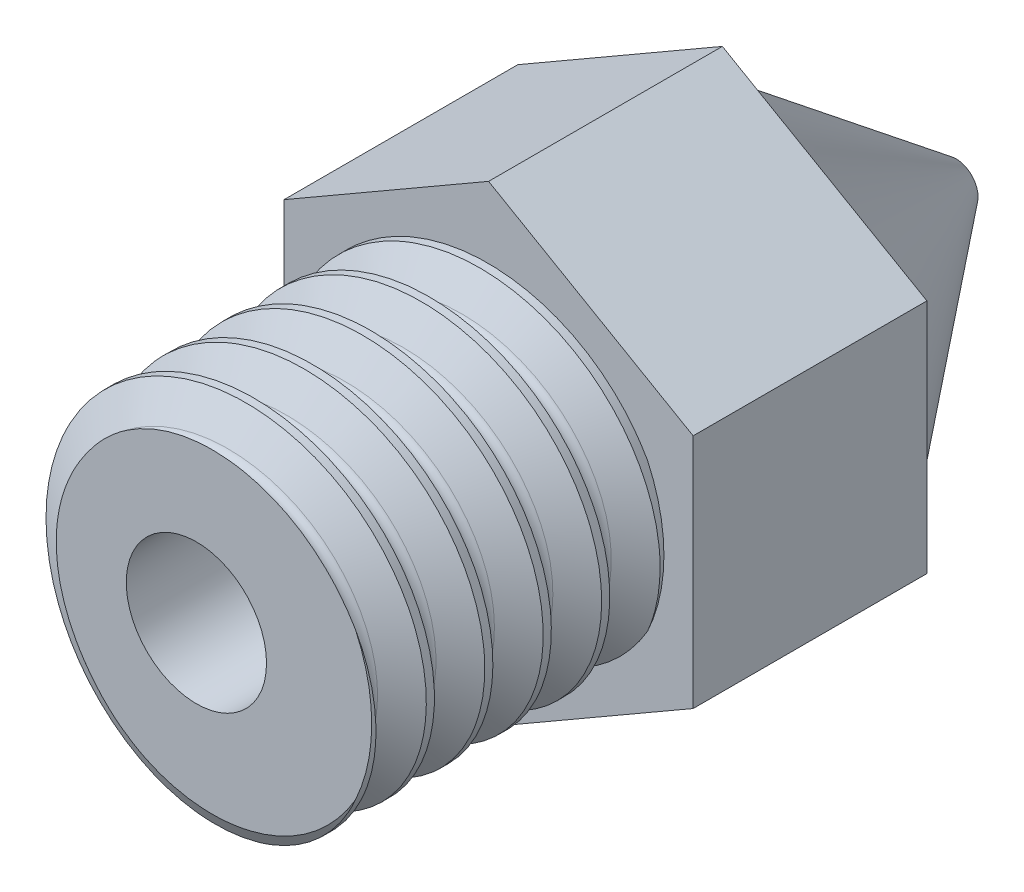
SolidWorks part; units mm, degrees
material "Brass"
ref_plane "Front Plane" through (0, 0, 0) normal (0, 0, 1) x (1, 0, 0)
ref_plane "Top Plane" through (0, 0, 0) normal (0, 1, 0) x (1, 0, 0)
ref_plane "Right Plane" through (0, 0, 0) normal (1, 0, 0) x (0, 0, -1)
sketch "Sketch1" plane through (0, 0, 0) normal (0, 0, 1) x (1, 0, 0)
  circle A0 centre (0, 0) radius 3
extrude "Boss-Extrude1" add sketch "Sketch1" along normal blind 5
sketch "Sketch2" plane through (0, 0, 5) normal (0, 0, 1) x (1, 0, 0)
  circle A0 centre (0, 0) radius 3
curve "Helix/Spiral1" pitch 1 height 6.25 turns 6.25
sketch "Sketch3" plane through (0, 0, 0) normal (0, 1, 0) x (1, 0, 0)
  line L0 (0, -5) -> (-2.5, -5) construction
  line L1 (-2.4701, -4.8753) -> (-3.0335, -4.55)
  line L2 (-3.0335, -4.55) -> (-3.0335, -5.45)
  line L3 (-3.0335, -5.45) -> (-2.4701, -5.1247)
  line L4 (-3, -5) -> (3, -5) construction
  line L5 (-3, -5) -> (-3, -5.48) construction
  line L6 (-3, -5.48) -> (-3, -5) construction
  circle A0 centre (-2.7737, -5) radius 0.2598 construction
  arc A1 (-2.4701, -4.8753) -> (-2.4701, -5.1247) centre (-2.5421, -5) cw
  point P14 (-2.2541, -5)
  dimension "D1" = 0.144
sweep "Cut-Sweep2" cut profiles "Sketch3" path "Helix/Spiral1"
sketch "Sketch4" plane through (0, 0, 0) normal (0, 0, -1) x (-1, 0, 0)
  line L1 (0, 4.0415) -> (-3.5, 2.0207)
  line L2 (-3.5, 2.0207) -> (-3.5, -2.0207)
  line L3 (-3.5, -2.0207) -> (0, -4.0415)
  line L4 (0, -4.0415) -> (3.5, -2.0207)
  line L5 (3.5, -2.0207) -> (3.5, 2.0207)
  line L6 (3.5, 2.0207) -> (0, 4.0415)
  circle A0 centre (0, 0) radius 3.5 construction
extrude "Boss-Extrude2" add sketch "Sketch4" along normal blind 4
sketch "Sketch5" plane through (0, 0, -4) normal (0, 0, -1) x (-1, 0, 0)
  circle A0 centre (0, 0) radius 3.5
extrude "Boss-Extrude3" add sketch "Sketch5" along normal blind 4 draft 38
hole_wizard "Ø2.4 (2.4) Diameter Hole1" positions "Sketch9" profile "Sketch8" hole size "Ø2.4" standard "Ansi Metric"
sketch "Sketch9" plane through (0, 0, 5) normal (0, 0, 1) x (1, 0, 0)
  point P0 (0, 0)
sketch "Sketch8" plane through (0, 0, 5) normal (1, 0, 0) x (0, -1, 0)
  line L0 (0, 0) -> (0, 11.511)
  line L1 (0, 11.511) -> (1.2, 10.79)
  line L2 (1.2, 10.79) -> (1.2, 0)
  line L5 (1.2, 0) -> (0, 0)
  line L10 (0, 11.511) -> (-1.2, 10.79) construction
  line L11 (0, -6.35) -> (0, 107.95) construction
  dimension "Hole Dia." = 2.4
  dimension "Hole Depth" = 10.79
  dimension "Drill Angle" = 118
sketch "Sketch10" plane through (0, 0, -8) normal (0, 0, -1) x (-1, 0, 0)
  circle A0 centre (0, 0) radius 0.1
extrude "Cut-Extrude1" cut sketch "Sketch10" against normal blind 5
